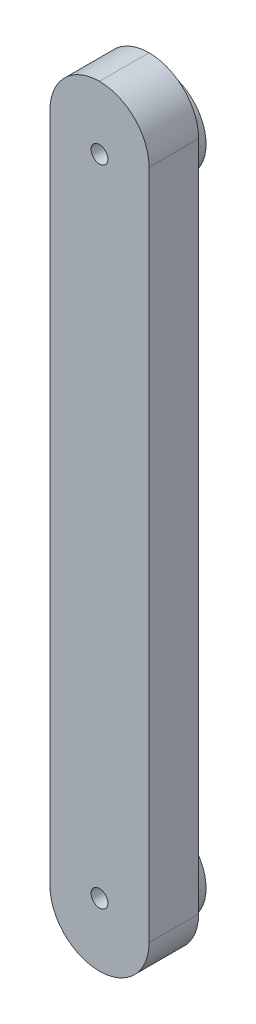
SolidWorks part; units mm, degrees
material "PETG"
ref_plane "Front Plane" through (0, 0, 0) normal (0, 0, 1) x (1, 0, 0)
ref_plane "Top Plane" through (0, 0, 0) normal (0, 1, 0) x (1, 0, 0)
ref_plane "Right Plane" through (0, 0, 0) normal (1, 0, 0) x (0, 0, -1)
sketch "Sketch1" plane through (0, 0, 0) normal (0, 0, 1) x (1, 0, 0)
  line L1 (-10, 77.75) -> (10, 77.75)
  line L2 (-10, 77.75) -> (-10, -77.75)
  line L3 (-10, -77.75) -> (10, -77.75)
  line L4 (10, 77.75) -> (10, -77.75)
  point P8 (-10, 0)
  point P9 (0, 77.75)
  dimension "D1" = 20
  dimension "D2" = 155.5
extrude "Boss-Extrude1" add sketch "Sketch1" along normal blind 10
sketch "Sketch2" plane through (0, 0, 0) normal (0, 0, -1) x (-1, 0, 0)
  line L0 (0, 65) -> (0, -65) construction
  circle A0 centre (0, 65) radius 9
  circle A1 centre (0, -65) radius 9
  dimension "D1" = 130
  dimension "D2" = 18
extrude "Boss-Extrude2" add sketch "Sketch2" along normal blind 2.5
sketch "Sketch3" plane through (0, 0, -2.5) normal (0, 0, -1) x (-1, 0, 0)
  circle A0 centre (0, 65) radius 1.7
  circle A1 centre (0, -65) radius 1.7
  circle A2 centre (0, -65) radius 9 construction
  circle A3 centre (0, 65) radius 9 construction
  dimension "D1" = 3.4
extrude "Cut-Extrude1" cut sketch "Sketch3" against normal through all
fillet "Fillet1" radius 10 4 edges at (10, -77.75, 5) (-10, -77.75, 5) (-10, 77.75, 5) (10, 77.75, 5)
equation "\"tol_dia_id_intfc\" = 0.0500mm ' For hole diameters - Interference fit"
equation "\"tol_dia_id_slip\"  = 0.0750mm ' For hole diameters - Slip fit"
equation "\"tol_dia_id_clear\" = 0.1000mm ' For hole diameters - Clearance fit"
equation "\"tol_dia_od_intfc\" = 0.0500mm ' For shaft diameters - Interference fit"
equation "\"tol_dia_od_slip\"  = 0.0750mm ' For shaft diameters - Slip fit"
equation "\"tol_dia_od_clear\" = 0.1000mm ' For shaft diameters - Clearance fit"
equation "\"tol_general_intfc\"= 0.0250mm ' For general parts (Horiz) - Interference fit"
equation "\"tol_general_slip\" = 0.0375mm ' For general parts (Horiz) - Slip fit"
equation "\"tol_general_clear\"= 0.0500mm ' For general parts (Horiz) - Clearance fit"
equation "\"tol_layer_intfc\"  = 0.0250mm ' For all parts (Vert) - Interference fit"
equation "\"tol_layer_slip\"   = 0.0375mm ' For all parts (Vert) - Slip fit"
equation "\"tol_layer_clear\"  = 0.0500mm ' For all parts (Vert) - Clearance fit"
equation "\"tol_corner_rad\"   = 0.100mm ' For corners that fit into other parts"
